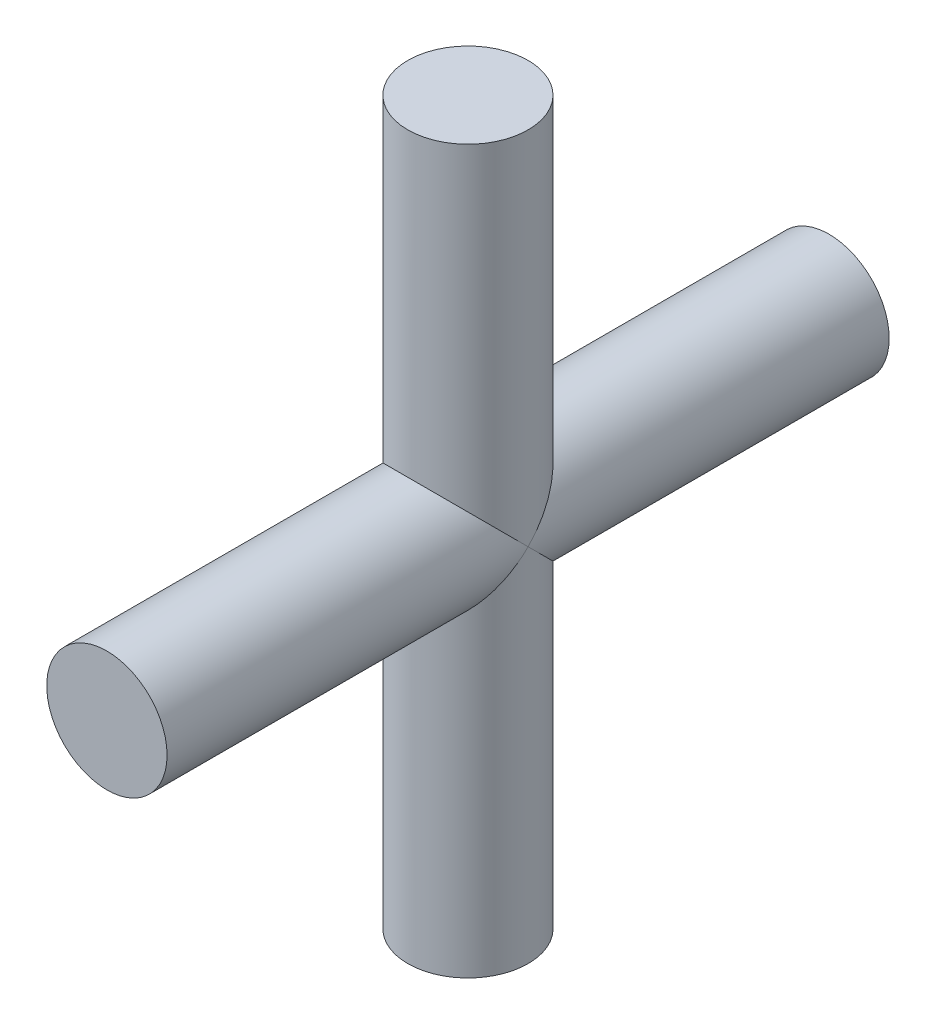
SolidWorks part; units mm, degrees
ref_plane "Front Plane" through (0, 0, 0) normal (0, 0, 1) x (1, 0, 0)
ref_plane "Top Plane" through (0, 0, 0) normal (0, 1, 0) x (1, 0, 0)
ref_plane "Right Plane" through (0, 0, 0) normal (1, 0, 0) x (0, 0, -1)
sketch "Sketch1" plane through (0, 0, 0) normal (0, 1, 0) x (1, 0, 0)
  line L0 (0, 0) -> (-6.096, 0) construction
  line L1 (-1.016, 0) -> (0, 0)
  line L2 (0, 0) -> (0, 6.096)
  line L3 (-1.016, 0) -> (-1.016, 6.096)
  line L4 (-1.016, 6.096) -> (0, 6.096)
  line L5 (0, 0) -> (0, 6.7937) construction
  dimension "D2" = 1.016
  dimension "D4" = 6.096
revolve "Revolve2" add sketch "Sketch1" angle 360 about L2
sketch "Sketch2" plane through (0, 0, 0) normal (0, 1, 0) x (1, 0, 0)
  circle A0 centre (0, 0) radius 1.016
extrude "Boss-Extrude1" add sketch "Sketch2" along normal blind 6.096 and the other way blind 6.096
sketch "Sketch3" plane through (0, 0, 0) normal (0, 0, 1) x (1, 0, 0)
  circle A0 centre (0, 0) radius 1.016
extrude "Boss-Extrude2" add sketch "Sketch3" along normal blind 6.096
